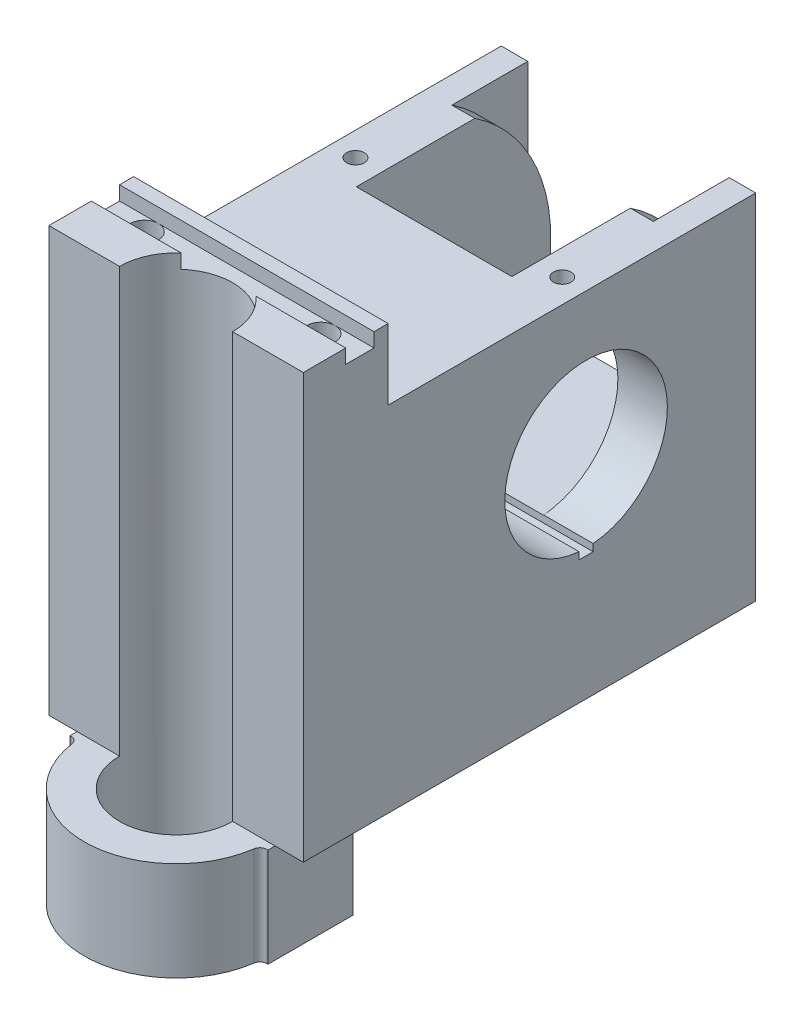
SolidWorks part; units mm, degrees
ref_plane "Front Plane" through (0, 0, 0) normal (0, 0, 1) x (1, 0, 0)
ref_plane "Top Plane" through (0, 0, 0) normal (0, 1, 0) x (1, 0, 0)
ref_plane "Right Plane" through (0, 0, 0) normal (1, 0, 0) x (0, 0, -1)
sketch "Sketch1" plane through (0, 0, 0) normal (1, 0, 0) x (0, 0, -1)
  line L0 (0, 0) -> (406.4, 0)
  line L1 (406.4, 0) -> (406.4, 317.5)
  line L2 (406.4, 317.5) -> (76.2, 317.5)
  line L3 (76.2, 317.5) -> (76.2, 381)
  line L4 (76.2, 381) -> (63.5, 381)
  line L5 (0, 381) -> (0, 0)
  line L6 (231.775, 317.5) -> (231.775, 117.475)
  line L7 (231.775, 117.475) -> (406.4, 117.475)
  line L8 (69.85, 0) -> (69.85, -88.9)
  line L9 (69.85, -88.9) -> (-82.55, -88.9)
  line L10 (-82.55, -88.9) -> (-82.55, 0)
  line L11 (-82.55, 0) -> (0, 0)
  line L12 (38.1, 381) -> (38.1, 368.3)
  line L13 (38.1, 368.3) -> (63.5, 368.3)
  line L14 (63.5, 368.3) -> (63.5, 381)
  line L15 (38.1, 381) -> (0, 381)
  line L16 (254, 117.475) -> (254, 111.4016)
  line L17 (247.65, 111.4016) -> (260.35, 111.4016)
  line L18 (260.35, 111.4016) -> (260.35, 117.7516)
  line L19 (247.65, 111.4016) -> (247.65, 117.7516)
  arc A0 (406.4, 190.5) -> (338.2423, 317.5) centre (254, 190.5) ccw
  circle A1 centre (254, 190.5) radius 73.025
  dimension "D8" = 304.8
  dimension "D14" = 146.05
  dimension "D1" = 406.4
  dimension "D2" = 317.5
  dimension "D3" = 63.5
  dimension "D4" = 76.2
  dimension "D5" = 174.625
  dimension "D6" = 200.025
  dimension "D7" = 152.4
  dimension "D9" = 127
  dimension "D10" = 69.85
  dimension "D11" = 25.4
  dimension "D12" = 82.55
  dimension "D13" = 88.9
  dimension "D15" = 127
  dimension "D16" = 152.4
  dimension "D17" = 38.1
  dimension "D18" = 12.7
  dimension "D19" = 6.35
  dimension "D20" = 6.35
extrude "Boss-Extrude2" add sketch "Sketch1" along normal blind 69.85 contours L7 L6 L2 L3 L4 L5 L0 L1 | L9 L8 L0 L11 | L9 L11 L10 | A1 L6 L7 region at (0, 144.1761, -151.3543) region at (0, -44.45, 6.35) region at (0, 118.5323, -237.0234)
extrude "Boss-Extrude3" add sketch "Sketch1<4>" along normal blind 20.6375 from vertex contours L1 A0 L2 L6 L7 | L7 L6 L2 L3 L4 L5 L0 L1 | A1 L6 L7 region at (0, 144.1761, -151.3543) region at (0, 224.02, -336.2535) region at (0, 118.5323, -237.0234) starting at point (69.85, 317.5, -231.775)
sketch "Sketch1<4>" plane through (0, 0, 0) normal (1, 0, 0) x (0, 0, -1) same geometry as "Sketch1"
extrude "Boss-Extrude4" add sketch "Sketch1<5>" along normal blind 23.8125 from vertex contours L7 L6 L2 L3 L4 L5 L0 L1 | A0 L1 L2 | L1 A0 L2 L6 L7 | A1 L6 L7 region at (0, 144.1761, -151.3543) region at (0, 224.02, -336.2535) region at (0, 287.3424, -387.0753) region at (0, 118.5323, -237.0234) starting at point (90.4875, 317.5, -76.2)
sketch "Sketch1<5>" plane through (0, 0, 0) normal (1, 0, 0) x (0, 0, -1) same geometry as "Sketch1"
extrude "Boss-Extrude5" add sketch "Sketch1<6>" along normal blind 19.05 from vertex contours L9 L8 L0 L11 | L9 L11 L10 region at (0, -44.45, 6.35) starting at point (69.85, 0, 82.55)
sketch "Sketch1<6>" plane through (0, 0, 0) normal (1, 0, 0) x (0, 0, -1) same geometry as "Sketch1"
mirror "Mirror2" about plane through (0, 0, 0) normal (1, 0, 0) of "Boss-Extrude4", "Boss-Extrude5", "Boss-Extrude3", "Boss-Extrude2"
sketch "Sketch2" plane through (0, 381, 0) normal (0, 1, 0) x (1, 0, 0)
  line L0 (-88.9, -88.9) -> (88.9, -88.9)
  line L1 (88.9, -88.9) -> (88.9, -6.35)
  line L2 (88.9, -82.55) -> (88.9, 0) construction
  line L3 (88.9, -6.35) -> (87.9882, -6.35)
  line L4 (-88.9, -88.9) -> (-88.9, -6.35)
  line L5 (-88.9, -82.55) -> (-88.9, 0) construction
  line L6 (-88.9, -6.35) -> (-87.9882, -6.35)
  line L7 (88.9, 69.85) -> (-88.9, 69.85) construction
  circle A0 centre (0, 0) radius 50.8
  arc A1 (-81.7033, -11.7929) -> (81.7033, -11.7929) centre (0, 0) ccw
  arc A2 (87.9882, -6.35) -> (81.7033, -11.7929) centre (87.9882, -12.7) ccw
  arc A3 (-87.9882, -6.35) -> (-81.7033, -11.7929) centre (-87.9882, -12.7) cw
  point P9 (82.3054, -6.35)
  dimension "D1" = 101.6
  dimension "D2" = 165.1
  dimension "D5" = 6.35
  dimension "D3" = 76.2
  dimension "D4" = 82.55
extrude "Cut-Extrude1" cut sketch "Sketch2" against normal through all contours A3 L6 L4 L0 L1 L3 A2 A1 | A0 | A0 region at (-86.9397, 381, 47.625) region at (0, 381, 0)
sketch "Sketch3" plane through (0, 368.3, 0) normal (0, 1, 0) x (1, 0, 0)
  line L0 (-114.3, 50.8) -> (114.3, 50.8) construction
  line L1 (-114.3, 38.1) -> (-114.3, 63.5) construction
  line L2 (114.3, 38.1) -> (114.3, 63.5) construction
  circle A0 centre (-79.375, 50.8) radius 12.7
  circle A1 centre (79.375, 50.8) radius 12.7
  dimension "D1" = 25.4
  dimension "D2" = 79.375
  dimension "D3" = 158.75
extrude "Cut-Extrude2" cut sketch "Sketch3" against normal blind 38.1
sketch "Sketch4" plane through (0, 317.5, 0) normal (0, 1, 0) x (1, 0, 0)
  line L0 (-114.3, 406.4) -> (-114.3, 76.2) construction
  line L1 (114.3, 406.4) -> (114.3, 76.2) construction
  line L2 (-69.85, 254) -> (-114.3, 254) construction
  circle A0 centre (-92.8688, 254) radius 7.9375
  circle A1 centre (92.8688, 254) radius 7.9375
  point P10 (-92.8688, 254)
  dimension "D1" = 15.875
  dimension "D2" = 21.4312
  dimension "D3" = 21.4312
extrude "Cut-Extrude3" cut sketch "Sketch4" against normal up to next contours A0 | A1 region at (-92.8688, 317.5, -254) region at (92.8688, 317.5, -254)
